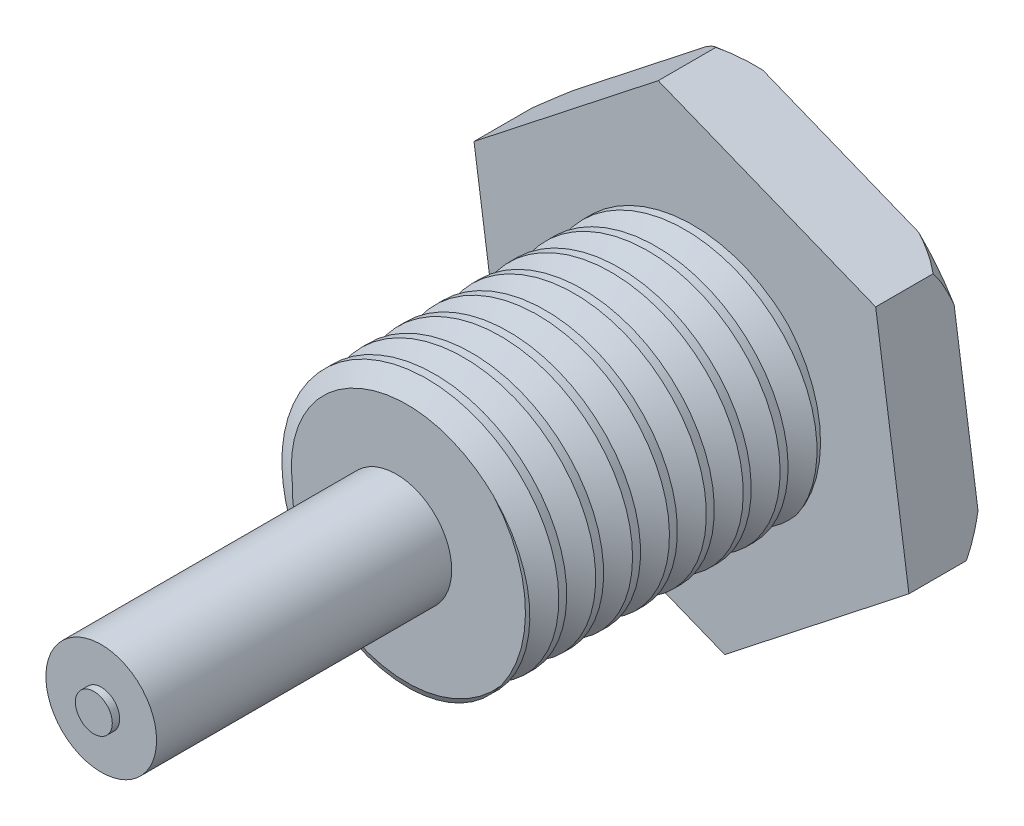
SolidWorks part; units mm, degrees
ref_plane "Front Plane" through (0, 0, 0) normal (0, 0, 1) x (1, 0, 0)
ref_plane "Top Plane" through (0, 0, 0) normal (0, 1, 0) x (1, 0, 0)
ref_plane "Right Plane" through (0, 0, 0) normal (1, 0, 0) x (0, 0, -1)
sketch "Sketch1" plane through (0, 0, 0) normal (0, 0, 1) x (1, 0, 0)
  circle A0 centre (0, 0) radius 0.875
  dimension "D1" = 1.75
extrude "Boss-Extrude1" add sketch "Sketch1" along normal blind 2
sketch "Sketch2" plane through (0, 0, 0) normal (0, 0, -1) x (-1, 0, 0)
  line L1 (-0.2253, -1.5717) -> (1.2485, -0.9809)
  line L2 (1.2485, -0.9809) -> (1.4737, 0.5907)
  line L3 (1.4737, 0.5907) -> (0.2253, 1.5717)
  line L4 (0.2253, 1.5717) -> (-1.2485, 0.9809)
  line L5 (-1.2485, 0.9809) -> (-1.4737, -0.5907)
  line L6 (-1.4737, -0.5907) -> (-0.2253, -1.5717)
  circle A0 centre (0, 0) radius 1.375 construction
  dimension "D1" = 2.75
extrude "Boss-Extrude2" add sketch "Sketch2" along normal blind 0.5
sketch "Sketch3" plane through (0, 0, 2) normal (0, 0, 1) x (1, 0, 0)
  circle A0 centre (0, 0) radius 0.375
  circle A1 centre (0, 0) radius 0.875 construction
  dimension "D1" = 0.75
extrude "Boss-Extrude3" add sketch "Sketch3" along normal blind 2
sketch "Sketch4" plane through (0, 0, 2) normal (0, 0, 1) x (1, 0, 0)
  circle A0 centre (0, 0) radius 0.875 construction
  circle A1 centre (0, 0) radius 0.875
curve "Helix/Spiral1" pitch 0.25 height 2 radius 0.875 centre (0, 0, 2) axis (0, 0, -1) start towards (-1, 0, 0)
sketch "Sketch5" plane through (0, 0, 4) normal (0, 0, 1) x (1, 0, 0)
  circle A1 centre (0, 0) radius 0.125
  dimension "D1" = 0.25
ref_plane "Plane1" through (-0.875, 0, 2) normal (0, 0.999, -0.0454) x (1, 0, 0)
sketch "Sketch6" plane through (-0.875, 0, 2) normal (0, 0.999, -0.0454) x (1, 0, 0)
  line L0 (-0.3735, 2.542) -> (-0.3735, 2.0425) construction
  line L1 (0.1697, 0.002) -> (-0.0208, 0.112)
  line L2 (-0.0208, 0.112) -> (-0.0208, -0.108)
  line L3 (-0.0208, -0.108) -> (0.1697, 0.002)
  circle A0 centre (0.0427, 0.002) radius 0.0635 construction
  point P7 (0.0427, 0.002)
  dimension "D1" = 0.22
sweep "Cut-Sweep1" cut profiles "Sketch6" path "Helix/Spiral1" align with end faces yes
extrude "Boss-Extrude5" add sketch "Sketch5" along normal blind 0.05
sketch "Sketch7" plane through (0, 0, -0.5) normal (0, 0, -1) x (-1, 0, 0)
  circle A0 centre (0, 0) radius 1.5877
ref_plane "Plane2" through (0, 0, 0) normal (-0.6178, 0.7863, 0) x (0.7863, 0.6178, 0)
sketch "Sketch8" plane through (0, 0, 0) normal (-0.6178, 0.7863, 0) x (0.7863, 0.6178, 0)
  line L0 (-1.3481, 0.5796) -> (-1.6368, 0.5796)
  line L1 (-1.6368, 0.5796) -> (-1.6368, 0.2806)
  spline S0 degree 3 poles (-1.6368, 0.2806) (-1.619, 0.3908) (-1.4618, 0.5544) (-1.3481, 0.5796) knots 0 0 0 0 1 1 1 1
sweep "Cut-Sweep2" cut profiles "Sketch8" path "Sketch7"
